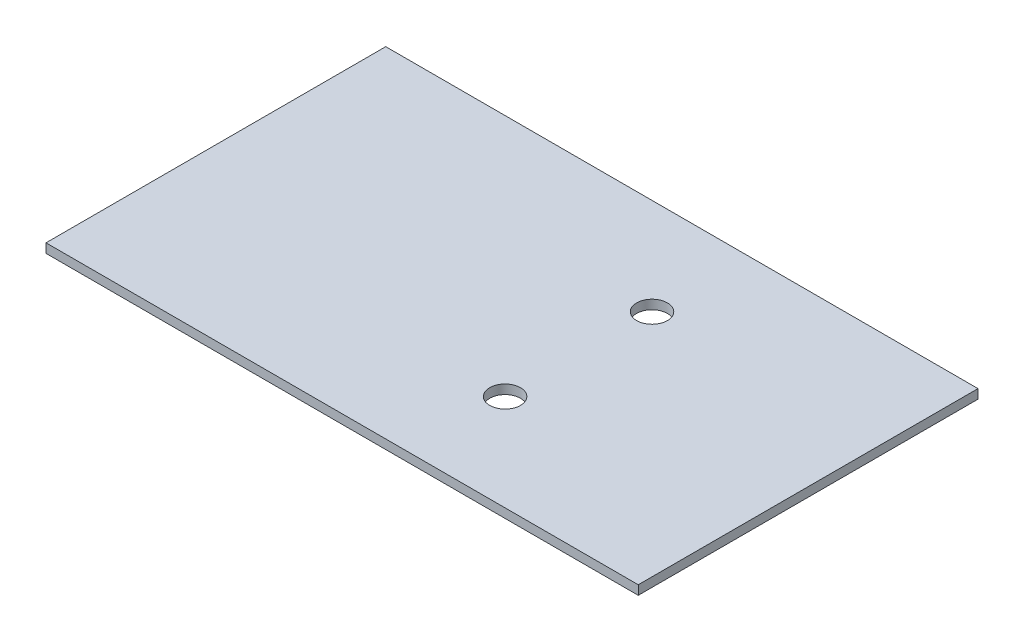
SolidWorks part; units mm, degrees
material "Acrylic (Medium-high impact)"
ref_plane "Front Plane" through (0, 0, 0) normal (0, 0, 1) x (1, 0, 0)
ref_plane "Top Plane" through (0, 0, 0) normal (0, 1, 0) x (1, 0, 0)
ref_plane "Right Plane" through (0, 0, 0) normal (1, 0, 0) x (0, 0, -1)
sketch "Sketch1" plane through (0, 0, 0) normal (0, 1, 0) x (1, 0, 0)
  line L1 (0, 0) -> (129, 0)
  line L2 (0, 0) -> (0, -74)
  line L3 (0, -74) -> (129, -74)
  line L4 (129, 0) -> (129, -74)
  dimension "D1" = 129
  dimension "D2" = 74
extrude "Boss-Extrude1" add sketch "Sketch1" along normal blind 2
sketch "Sketch2" plane through (0, 0, 0) normal (0, -1, 0) x (1, 0, 0)
  line L0 (129, 74) -> (129, 0) construction
  line L1 (0, 74) -> (129, 74) construction
  line L2 (129, 0) -> (0, 0) construction
  circle A0 centre (79, 21) radius 3.35
  circle A1 centre (79, 53) radius 3.35
  dimension "D1" = 6.7
  dimension "D2" = 6.7
  dimension "D3" = 50
  dimension "D4" = 21
  dimension "D5" = 50
  dimension "D6" = 21
extrude "Cut-Extrude1" cut sketch "Sketch2" against normal through all
